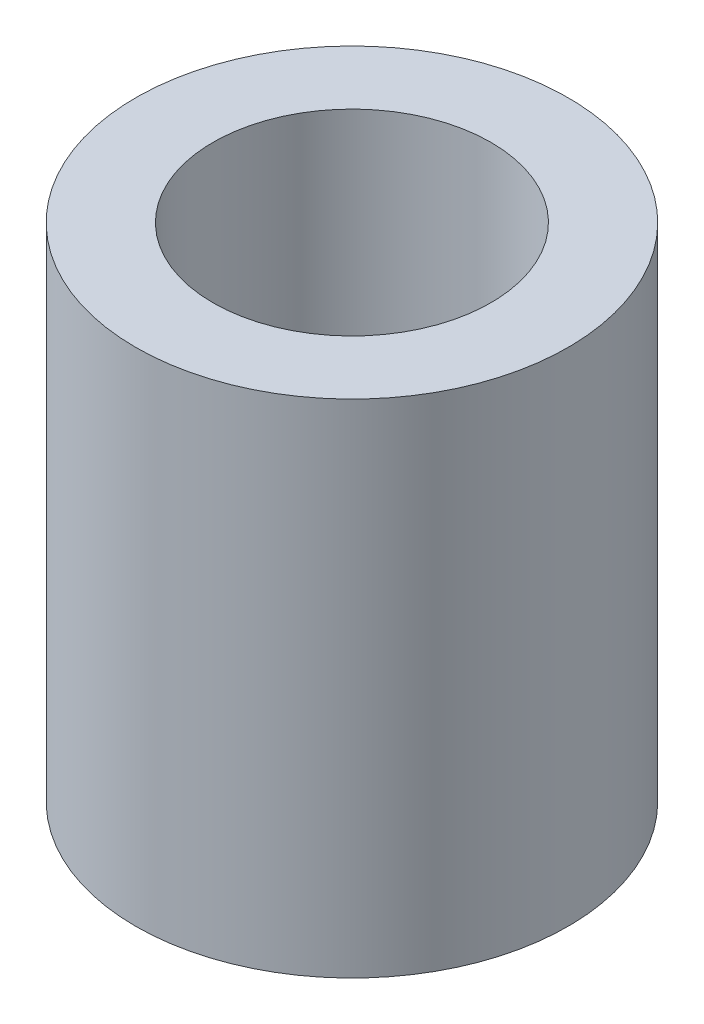
SolidWorks part; units mm, degrees
ref_plane "Front Plane" through (0, 0, 0) normal (0, 0, 1) x (1, 0, 0)
ref_plane "Top Plane" through (0, 0, 0) normal (0, 1, 0) x (1, 0, 0)
ref_plane "Right Plane" through (0, 0, 0) normal (1, 0, 0) x (0, 0, -1)
sketch "Sketch1" plane through (0, 0, 0) normal (0, 1, 0) x (1, 0, 0)
  circle A0 centre (0, 0) radius 6.9
  dimension "D1" = 13.8
extrude "Boss-Extrude1" add sketch "Sketch1" along normal blind 16
sketch "Sketch2" plane through (0, 16, 0) normal (0, 1, 0) x (1, 0, 0)
  circle A0 centre (0, 0) radius 4.435
  dimension "D1" = 8.87
extrude "Cut-Extrude1" cut sketch "Sketch2" against normal offset from surface (14 mm away) 2 up to face at (0, 0, 6.9)
